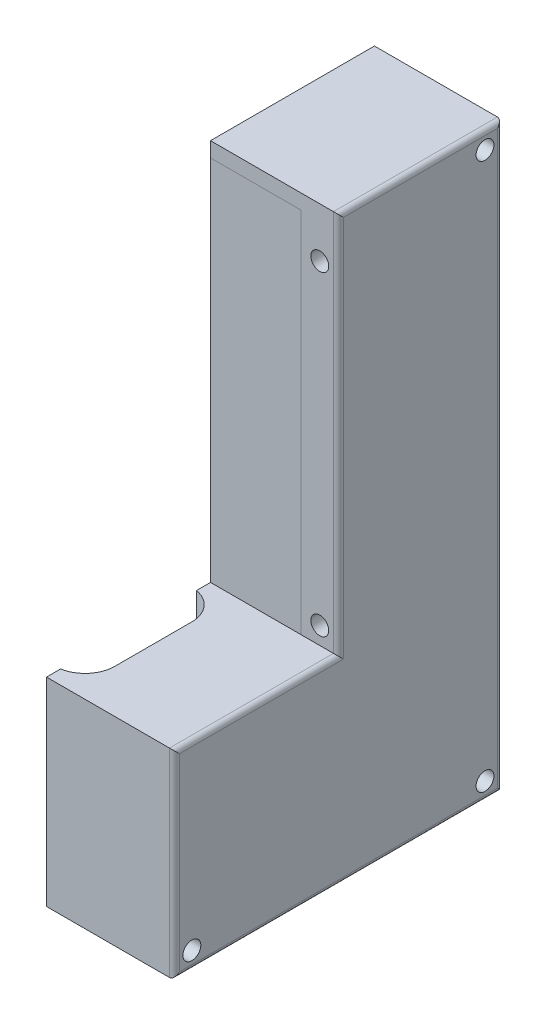
SolidWorks part; units mm, degrees
material "ABS"
ref_plane "Front" through (0, 0, 0) normal (0, 0, 1) x (1, 0, 0)
ref_plane "Top" through (0, 0, 0) normal (0, 1, 0) x (1, 0, 0)
ref_plane "Right" through (0, 0, 0) normal (1, 0, 0) x (0, 0, -1)
sketch "ｽｹｯﾁ1" plane through (0, 0, 0) normal (1, 0, 0) x (0, 0, -1)
  line L0 (23, 92) -> (0, 92)
  line L1 (33, 92) -> (23, 92)
  line L2 (33, 92) -> (33, -25)
  line L3 (33, -25) -> (23, -25)
  line L4 (23, 92) -> (23, -25)
  line L5 (0, 92) -> (0, -25)
  line L6 (0, -25) -> (23, -25)
  line L7 (0, -25) -> (-33, -25)
  line L8 (-33, -25) -> (-33, 0)
  line L9 (-33, 0) -> (0, 0)
  dimension "D1" = 117
  dimension "D2" = 10
  dimension "D3" = 33
  dimension "D4" = 23
  dimension "D5" = 25
extrude "ﾎﾞｽ - 押し出し1" add sketch "ｽｹｯﾁ1" along normal blind 77 contours L9 L8 L7 L5 | L5 L6 L4 L0 | L1 L4 L3 L2 region at (0, 33.5, -11.5) region at (0, 33.5, -28) region at (0, -12.5, 16.5)
sketch "ｽｹｯﾁ2" plane through (0, 0, -33) normal (0, 0, -1) x (-1, 0, 0)
  line L1 (-7.5, 22.5) -> (-69.5, 22.5)
  line L2 (-7.5, 22.5) -> (-7.5, 84.5)
  line L3 (-7.5, 84.5) -> (-69.5, 84.5)
  line L4 (-69.5, 22.5) -> (-69.5, 84.5)
  line L5 (-7.5, 22.5) -> (-69.5, 84.5) construction
  line L6 (-7.5, 84.5) -> (-69.5, 22.5) construction
  line L8 (0, 92) -> (0, -25) construction
  line L9 (-77, 92) -> (0, 92) construction
  point P0 (-38.5, 53.5)
  dimension "D1" = 62
  dimension "D2" = 62
  dimension "D3" = 7.5
  dimension "D4" = 7.5
extrude "ｶｯﾄ - 押し出し1" cut sketch "ｽｹｯﾁ2" against normal blind 10
sketch "ｽｹｯﾁ3" plane through (0, 92, 0) normal (0, 1, 0) x (1, 0, 0)
  line L1 (0, 33) -> (0, 0) construction
  line L2 (77, 0) -> (0, 0) construction
  circle A0 centre (37.5, 10.5) radius 8.1
  dimension "D1" = 16.2
  dimension "D2" = 37.5
  dimension "D3" = 10.5
extrude "ｶｯﾄ - 押し出し2" cut sketch "ｽｹｯﾁ3" against normal blind 10
sketch "ｽｹｯﾁ4" plane through (0, 0, -33) normal (0, 0, -1) x (-1, 0, 0)
  line L0 (-77, -25) -> (0, -25) construction
  line L1 (-7.5, 22.5) -> (-69.5, 22.5)
  line L2 (-7.5, 22.5) -> (-7.5, -17.5)
  line L3 (-7.5, -17.5) -> (-69.5, -17.5)
  line L4 (-69.5, 22.5) -> (-69.5, -17.5)
  dimension "D1" = 7.5
extrude "ｶｯﾄ - 押し出し3" cut sketch "ｽｹｯﾁ4" against normal offset from surface (58.5 mm away) 7.5 up to face at (38.5, -12.5, 33)
sketch "ｽｹｯﾁ5" plane through (0, 0, 0) normal (0, 1, 0) x (1, 0, 0)
  line L1 (50.25, -2.75) -> (24.75, -2.75)
  line L2 (56.25, -8.75) -> (56.25, -24.25)
  line L3 (50.25, -30.25) -> (24.75, -30.25)
  line L4 (18.75, -8.75) -> (18.75, -24.25)
  line L5 (56.25, -2.75) -> (18.75, -30.25) construction
  line L6 (56.25, -30.25) -> (18.75, -2.75) construction
  line L7 (0, -33) -> (0, 0) construction
  line L11 (77, -33) -> (0, -33)
  line L12 (77, -33) -> (77, 0)
  line L13 (77, 0) -> (0, 0)
  line L14 (0, -33) -> (0, 0)
  arc A0 (18.75, -8.75) -> (24.75, -2.75) centre (24.75, -8.75) cw
  arc A1 (56.25, -8.75) -> (50.25, -2.75) centre (50.25, -8.75) ccw
  arc A2 (56.25, -24.25) -> (50.25, -30.25) centre (50.25, -24.25) cw
  arc A3 (24.75, -30.25) -> (18.75, -24.25) centre (24.75, -24.25) cw
  point P0 (37.5, -16.5)
  dimension "D5" = 6
  dimension "D1" = 27.5
  dimension "D2" = 37.5
  dimension "D3" = 37.5
  dimension "D4" = 2.75
extrude "ﾎﾞｽ - 押し出し2" add sketch "ｽｹｯﾁ5" along normal blind 15
sketch "ｽｹｯﾁ6" plane through (0, 0, 0) normal (0, 1, 0) x (1, 0, 0)
  line L20 (43.25, -30.25) -> (43.25, -2.75)
  line L21 (51.25, -30.25) -> (51.25, -2.8339)
  line L22 (43.25, -25.5) -> (51.25, -25.5)
  line L24 (50.25, -2.75) -> (24.75, -2.75)
  line L25 (56.25, -24.25) -> (56.25, -8.75)
  line L26 (24.75, -30.25) -> (50.25, -30.25)
  line L27 (18.75, -8.75) -> (18.75, -24.25)
  line L28 (50.25, -2.75) -> (24.75, -2.75)
  line L29 (56.25, -24.25) -> (56.25, -8.75)
  line L30 (24.75, -30.25) -> (50.25, -30.25)
  line L31 (18.75, -8.75) -> (18.75, -24.25)
  line L32 (43.25, -7.5) -> (51.25, -7.5)
  arc A21 (24.75, -2.75) -> (18.75, -8.75) centre (24.75, -8.75) ccw
  arc A22 (56.25, -8.75) -> (50.25, -2.75) centre (50.25, -8.75) ccw
  arc A23 (50.25, -30.25) -> (56.25, -24.25) centre (50.25, -24.25) ccw
  arc A24 (18.75, -24.25) -> (24.75, -30.25) centre (24.75, -24.25) ccw
  arc A25 (24.75, -2.75) -> (18.75, -8.75) centre (24.75, -8.75) ccw
  arc A26 (56.25, -8.75) -> (50.25, -2.75) centre (50.25, -8.75) ccw
  arc A27 (50.25, -30.25) -> (56.25, -24.25) centre (50.25, -24.25) ccw
  arc A28 (18.75, -24.25) -> (24.75, -30.25) centre (24.75, -24.25) ccw
  arc M14 (18.8817, -25.5) -> (24.75, -30.25) centre (24.75, -24.25) ccw
  line M15 (24.75, -30.25) -> (50.25, -30.25)
  arc M16 (50.25, -30.25) -> (56.1183, -25.5) centre (50.25, -24.25) ccw
  line M17 (56.1183, -25.5) -> (18.8817, -25.5)
  dimension "D2" = 13
  dimension "D3" = 8
  dimension "D4" = 18
  dimension "D5" = 4.75
  dimension "D1" = 0
extrude "ﾎﾞｽ - 押し出し3" add sketch "ｽｹｯﾁ6" along normal blind 7 contours L31 A28 L20 L28 A25 M17 | L20 M15 M17 M14 | L21 L20 M16 M17 M15 | A27 L29 A26 L21 M17 | L21 M16 M17 | L21 A26 L28 L20 L32 region at (31.7692, 0, 27.8001) region at (47.2472, 0, 27.8733) region at (31.1546, 0, 14.265) region at (47.2472, 0, 5.1267) region at (53.1973, 0, 27.3736) region at (53.6635, 0, 14.8477)
sketch "ｽｹｯﾁ7" plane through (0, 0, 0) normal (0, 0, 1) x (1, 0, 0)
  line L0 (0, 92) -> (0, 15) construction
  line L1 (69.5, 89) -> (7.5, 89)
  line L2 (69.5, 89) -> (69.5, 22.5)
  line L3 (69.5, 22.5) -> (7.5, 22.5)
  line L4 (7.5, 89) -> (7.5, 22.5)
  line L5 (69.5, 89) -> (7.5, 22.5) construction
  line L6 (69.5, 22.5) -> (7.5, 89) construction
  line L7 (77, 92) -> (0, 92) construction
  line L9 (69.5, 22.5) -> (7.5, 22.5) construction
  line L10 (69.5, 84.5) -> (69.5, -17.5) construction
  point P0 (38.5, 55.75)
  dimension "D1" = 7.5
  dimension "D2" = 3
extrude "ｶｯﾄ - 押し出し4" cut sketch "ｽｹｯﾁ7" against normal offset from surface (20 mm away) 3 up to face at (38.5, 53.5, -23)
sketch "ｽｹｯﾁ8" plane through (0, 89, 0) normal (0, -1, 0) x (-1, 0, 0)
  line L0 (-69.5, 20) -> (-69.5, 0) construction
  line L1 (-7.5, 0) -> (-69.5, 0)
  line L2 (-7.5, 0) -> (-7.5, 2)
  line L3 (-7.5, 2) -> (-69.5, 2)
  line L4 (-69.5, 0) -> (-69.5, 2)
  dimension "D1" = 2
extrude "ﾎﾞｽ - 押し出し4" add sketch "ｽｹｯﾁ8" along normal up to vertex (89 mm away) separate body up to point (43.25, 0, 7.5)
sketch "ｽｹｯﾁ9" plane through (0, 0, 0) normal (-1, 0, 0) x (0, 0, 1)
  line L0 (-33, 92) -> (0, 92) construction
  line L1 (-33, 92) -> (-33, -25) construction
  line L2 (-33, -25) -> (33, -25) construction
  line L3 (33, -25) -> (33, 15) construction
  circle A0 centre (-29.5, 88.5) radius 1.8
  circle A1 centre (-29.5, -21.5) radius 1.8
  circle A2 centre (29.5, -21.5) radius 1.8
  dimension "D3" = 3.6
  dimension "D5" = 3.5
  dimension "D1" = 3.5
  dimension "D2" = 3.5
  dimension "D4" = 3.5
extrude "ｶｯﾄ - 押し出し5" cut sketch "ｽｹｯﾁ9" against normal through all
sketch "ｽｹｯﾁ10" plane through (0, 0, 0) normal (0, 0, 1) x (1, 0, 0)
  line L0 (77, 92) -> (0, 92) construction
  line L1 (7.5, 15) -> (0, 15) construction
  line L2 (0, 92) -> (0, 15) construction
  line L3 (77, 92) -> (77, 15) construction
  circle A0 centre (3.75, 82) radius 1.8
  circle A1 centre (73.25, 82) radius 1.8
  circle A2 centre (73.25, 18.5) radius 1.8
  circle A3 centre (3.75, 18.5) radius 1.8
  dimension "D3" = 3.6
  dimension "D1" = 3.5
  dimension "D2" = 10
  dimension "D4" = 3.75
  dimension "D5" = 3.75
extrude "ｶｯﾄ - 押し出し6" cut sketch "ｽｹｯﾁ10" against normal through all
sketch "ｽｹｯﾁ12" plane through (0, 0, -23) normal (0, 0, -1) x (-1, 0, 0)
  line L0 (-69.5, 84.5) -> (-69.5, 22.5) construction
  line L1 (-7.5, 84.5) -> (-69.5, 84.5) construction
  circle A0 centre (-66.5, 81.5) radius 1.8
  circle A1 centre (-11.5, 81.5) radius 1.8
  circle A2 centre (-11.5, 26.5) radius 1.8
  circle A3 centre (-66.5, 26.5) radius 1.8
  dimension "D3" = 3.6
  dimension "D1" = 55
  dimension "D2" = 55
  dimension "D4" = 3
  dimension "D5" = 3
extrude "ｶｯﾄ - 押し出し7" cut sketch "ｽｹｯﾁ12" against normal up to next (3 mm away)
sketch "ｽｹｯﾁ13" plane through (0, 0, -33) normal (0, 0, -1) x (-1, 0, 0)
  line L0 (0, 92) -> (0, -25) construction
  line L1 (0, 30.5) -> (-7.5, 30.5)
  line L2 (0, 30.5) -> (0, 42)
  line L3 (0, 42) -> (-7.5, 42)
  line L4 (-7.5, 30.5) -> (-7.5, 42)
  line L5 (-7.5, -17.5) -> (-7.5, 84.5) construction
  line L6 (-69.5, 22.5) -> (-7.5, 22.5) construction
  point P10 (-3.75, 42)
  dimension "D1" = 8
  dimension "D2" = 19.5
extrude "ｶｯﾄ - 押し出し8" cut sketch "ｽｹｯﾁ13" against normal blind 10
sketch "ｽｹｯﾁ15" plane through (0, 0, 0) normal (-1, 0, 0) x (0, 0, 1)
  line L20 (-23, 42) -> (-23, 30.5)
  line L21 (-23, 30.5) -> (-33, 30.5)
  line L22 (-33, 30.5) -> (-33, -25)
  line L23 (-33, -25) -> (33, -25)
  line L24 (33, -25) -> (33, 15)
  line L25 (33, 15) -> (0, 15)
  line L26 (0, 15) -> (0, 92)
  line L27 (0, 92) -> (-33, 92)
  line L28 (-33, 92) -> (-33, 42)
  line L29 (-33, 42) -> (-23, 42)
  line L30 (-23, 42) -> (-23, 30.5)
  line L31 (-23, 30.5) -> (-33, 30.5)
  line L32 (-33, 30.5) -> (-33, -25)
  line L33 (-33, -25) -> (33, -25)
  line L34 (33, -25) -> (33, 15)
  line L35 (33, 15) -> (0, 15)
  line L36 (0, 15) -> (0, 92)
  line L37 (0, 92) -> (-33, 92)
  line L38 (-33, 92) -> (-33, 42)
  line L39 (-33, 42) -> (-23, 42)
  dimension "D1" = 0
extrude "ｶｯﾄ - 押し出し9" cut sketch "ｽｹｯﾁ15" against normal blind 51.25
sketch "ｽｹｯﾁ17" plane through (0, -17.5, 0) normal (0, 1, 0) x (1, 0, 0)
  line L0 (51.25, 33) -> (51.25, -25.5) construction
  line L1 (69.5, -25.5) -> (51.25, -25.5)
  line L2 (69.5, -25.5) -> (69.5, 25.5)
  line L3 (69.5, 25.5) -> (51.25, 25.5)
  line L4 (51.25, -25.5) -> (51.25, 25.5)
  line L5 (69.5, 33) -> (51.25, 33) construction
  dimension "D1" = 7.5
extrude "ｶｯﾄ - 押し出し11" cut sketch "ｽｹｯﾁ17" against normal offset from surface (4.5 mm away) 3 up to face at (64.125, -25, 0)
sketch "ｽｹｯﾁ18" plane through (0, 0, 25.5) normal (0, 0, -1) x (-1, 0, 0)
  line L0 (-51.25, -22) -> (-51.25, 0) construction
  line L1 (-69.5, 0) -> (-51.25, 0)
  line L2 (-69.5, 0) -> (-69.5, -17.5)
  line L3 (-69.5, -17.5) -> (-51.25, -17.5)
  line L4 (-51.25, 0) -> (-51.25, -17.5)
  line L5 (-77, -25) -> (-51.25, -25) construction
  dimension "D1" = 7.5
extrude "ｶｯﾄ - 押し出し12" cut sketch "ｽｹｯﾁ18" against normal offset from surface (4.5 mm away) 3 up to face at (64.125, -5, 33)
sketch "ｽｹｯﾁ19" plane through (0, 0, -23) normal (0, 0, -1) x (-1, 0, 0)
  line L0 (-69.5, 22.5) -> (-51.25, 22.5) construction
  line L1 (-51.25, 84.5) -> (-63, 84.5)
  line L2 (-51.25, 84.5) -> (-51.25, 22.5)
  line L3 (-51.25, 22.5) -> (-63, 22.5)
  line L4 (-63, 84.5) -> (-63, 22.5)
  line L5 (-69.5, 84.5) -> (-69.5, 22.5) construction
  dimension "D1" = 6.5
extrude "ｶｯﾄ - 押し出し13" cut sketch "ｽｹｯﾁ19" against normal up to next (3 mm away)
fillet "ﾌｨﾚｯﾄ1" radius 1 6 edges at (77, 15, 16.5) (77, -5, 33) (77, -25, 0) (77, 33.5, -33) (77, 92, -16.5) (77, 53.5, 0)
